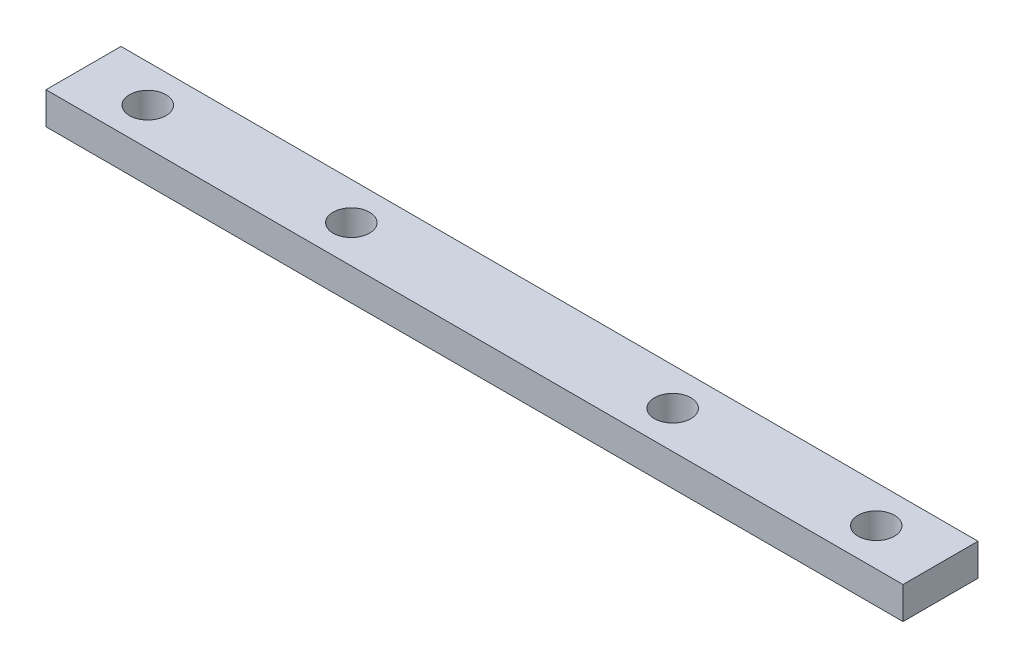
SolidWorks part; units mm, degrees
ref_plane "Front Plane" through (0, 0, 0) normal (0, 0, 1) x (1, 0, 0)
ref_plane "Top Plane" through (0, 0, 0) normal (0, 1, 0) x (1, 0, 0)
ref_plane "Right Plane" through (0, 0, 0) normal (1, 0, 0) x (0, 0, -1)
sketch "Sketch1" plane through (0, 0, 0) normal (0, 1, 0) x (1, 0, 0)
  line L1 (-40, -3.5) -> (40, -3.5)
  line L2 (-40, -3.5) -> (-40, 3.5)
  line L3 (-40, 3.5) -> (40, 3.5)
  line L4 (40, -3.5) -> (40, 3.5)
  line L5 (-40, -3.5) -> (40, 3.5) construction
  line L6 (-40, 3.5) -> (40, -3.5) construction
  point P0 (0, 0)
  dimension "D1" = 80
  dimension "D2" = 7
extrude "Boss-Extrude1" add sketch "Sketch1" along normal blind 3
sketch "Sketch2" plane through (0, 3, 0) normal (0, 1, 0) x (1, 0, 0)
  line L0 (-34, 0) -> (34, 0) construction
  line L3 (-15, 0) -> (15, 0) construction
  line L4 (-40, 3.5) -> (-40, -3.5) construction
  circle A0 centre (-34, 0) radius 1.7
  circle A1 centre (-15, 0) radius 1.7
  circle A2 centre (15, 0) radius 1.7
  circle A3 centre (34, 0) radius 1.7
  point P3 (0, 0)
  point P9 (0, 0)
  dimension "D3" = 3.4
  dimension "D1" = 30
  dimension "D2" = 6
extrude "Cut-Extrude1" cut sketch "Sketch2" against normal through all
